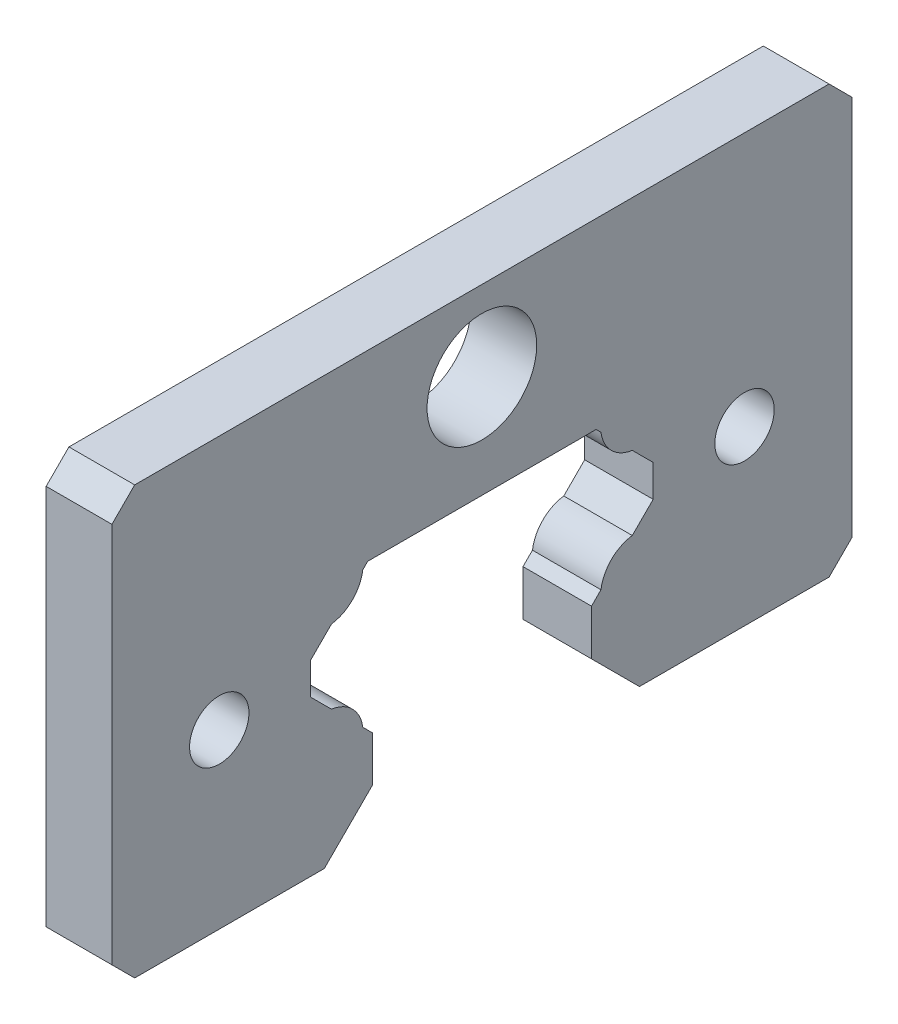
SolidWorks part; units mm, degrees
ref_plane "Спереди" through (0, 0, 0) normal (0, 0, 1) x (1, 0, 0)
ref_plane "Сверху" through (0, 0, 0) normal (0, 1, 0) x (1, 0, 0)
ref_plane "Сбоку" through (0, 0, 0) normal (1, 0, 0) x (0, 0, -1)
ref_plane "Плоскость1" through (0, 0, 0) normal (1, 0, 0) x (0, 0, -1)
sketch "Эскиз1" plane through (0, 0, 0) normal (1, 0, 0) x (0, 0, -1)
  line L0 (-16.2, 0.997) -> (-15.203, 0)
  line L1 (-15.203, 0) -> (15.203, 0)
  line L2 (15.203, 0) -> (16.2, 0.997)
  line L3 (16.2, 0.997) -> (16.2, 17.703)
  line L4 (16.2, 17.703) -> (15.203, 18.7)
  line L5 (15.203, 18.7) -> (-15.203, 18.7)
  line L6 (-15.203, 18.7) -> (-16.2, 17.703)
  line L7 (-16.2, 17.703) -> (-16.2, 0.997)
extrude "Бобышка-Вытянуть1" add sketch "Эскиз1" against normal blind 1.5 and the other way blind 1.5
ref_plane "Плоскость2" through (0, 0, 0) normal (1, 0, 0) x (0, 0, -1)
sketch "Эскиз2" plane through (0, 0, 0) normal (1, 0, 0) x (0, 0, -1)
  line L0 (-11.2, -4.3) -> (11.2, -4.3)
  line L1 (11.2, -4.3) -> (4.8, 2.1)
  line L2 (4.8, 2.1) -> (4.8, 4.1)
  line L3 (4.8, 4.1) -> (5.2144, 4.5144)
  line L4 (6.5856, 5.8856) -> (7.5, 6.8)
  line L5 (7.5, 6.8) -> (7.5, 8.2)
  line L6 (7.5, 8.2) -> (6.5856, 9.1144)
  line L7 (5.2144, 10.4856) -> (5, 10.7)
  line L8 (5, 10.7) -> (-5, 10.7)
  line L9 (-5, 10.7) -> (-5.2144, 10.4856)
  line L10 (-6.5856, 9.1144) -> (-7.5, 8.2)
  line L11 (-7.5, 8.2) -> (-7.5, 6.8)
  line L12 (-7.5, 6.8) -> (-6.5856, 5.8856)
  line L13 (-5.2144, 4.5144) -> (-4.8, 4.1)
  line L14 (-4.8, 4.1) -> (-4.8, 2.1)
  line L15 (-4.8, 2.1) -> (-11.2, -4.3)
  arc A0 (5.2144, 4.5144) -> (6.5856, 5.8856) centre (6.8, 4.3) cw
  arc A1 (6.5856, 9.1144) -> (5.2144, 10.4856) centre (6.8, 10.7) cw
  arc A2 (-5.2144, 10.4856) -> (-6.5856, 9.1144) centre (-6.8, 10.7) cw
  arc A3 (-6.5856, 5.8856) -> (-5.2144, 4.5144) centre (-6.8, 4.3) cw
extrude "Вырез-Вытянуть1" cut sketch "Эскиз2" against normal blind 1.5 and the other way blind 1.5
ref_plane "Плоскость3" through (-1.5, 0, 0) normal (1, 0, 0) x (0, 0, -1)
sketch "Эскиз3" plane through (-1.5, 0, 0) normal (1, 0, 0) x (0, 0, -1)
  line L0 (-16.2, -4.3) -> (-12.6142, -4.3)
  line L1 (-12.6142, -4.3) -> (-5.6, 2.7142)
  line L2 (-5.6, 2.7142) -> (-5.6, 3.7686)
  line L3 (-5.6, 3.7686) -> (-6.0236, 4.1922)
  line L4 (-6.9078, 5.0764) -> (-8.5, 6.6686)
  line L5 (-8.5, 6.6686) -> (-8.5, 8.3314)
  line L6 (-8.5, 8.3314) -> (-6.9078, 9.9236)
  line L7 (-6.0236, 10.8078) -> (-5.1314, 11.7)
  line L8 (-5.1314, 11.7) -> (5.1314, 11.7)
  line L9 (5.1314, 11.7) -> (6.0236, 10.8078)
  line L10 (6.9078, 9.9236) -> (8.5, 8.3314)
  line L11 (8.5, 8.3314) -> (8.5, 6.6686)
  line L12 (8.5, 6.6686) -> (6.9078, 5.0764)
  line L13 (6.0236, 4.1922) -> (5.6, 3.7686)
  line L14 (5.6, 3.7686) -> (5.6, 2.7142)
  line L15 (5.6, 2.7142) -> (12.6142, -4.3)
  line L16 (12.6142, -4.3) -> (16.2, -4.3)
  line L17 (16.2, -4.3) -> (16.2, 18.7)
  line L18 (16.2, 18.7) -> (-16.2, 18.7)
  line L19 (-16.2, 18.7) -> (-16.2, -4.3)
  arc A0 (-6.0236, 4.1922) -> (-6.9078, 5.0764) centre (-7.5071, 3.5929) ccw
  arc A1 (-6.9078, 9.9236) -> (-6.0236, 10.8078) centre (-7.5071, 11.4071) ccw
  arc A2 (6.0236, 10.8078) -> (6.9078, 9.9236) centre (7.5071, 11.4071) ccw
  arc A3 (6.9078, 5.0764) -> (6.0236, 4.1922) centre (7.5071, 3.5929) ccw
extrude "Вырез-Вытянуть2" cut sketch "Эскиз3" along normal blind 0.12
ref_plane "Плоскость4" through (-1.5, 0, 0) normal (1, 0, 0) x (0, 0, -1)
sketch "Эскиз4" plane through (-1.5, 0, 0) normal (1, 0, 0) x (0, 0, -1)
  circle A0 centre (0, 15.2) radius 2.4
extrude "Вырез-Вытянуть3" cut sketch "Эскиз4" along normal blind 3
ref_plane "Плоскость5" through (0, 0, 0) normal (1, 0, 0) x (0, 0, -1)
sketch "Эскиз5" plane through (0, 0, 0) normal (1, 0, 0) x (0, 0, -1)
  circle A0 centre (-11.5, 7.5556) radius 1.3
extrude "Вырез-Вытянуть4" cut sketch "Эскиз5" against normal blind 3 and the other way blind 3
ref_plane "Плоскость6" through (0, 0, 0) normal (1, 0, 0) x (0, 0, -1)
sketch "Эскиз6" plane through (0, 0, 0) normal (1, 0, 0) x (0, 0, -1)
  circle A0 centre (11.5, 7.5556) radius 1.3
extrude "Вырез-Вытянуть5" cut sketch "Эскиз6" against normal blind 3 and the other way blind 3
